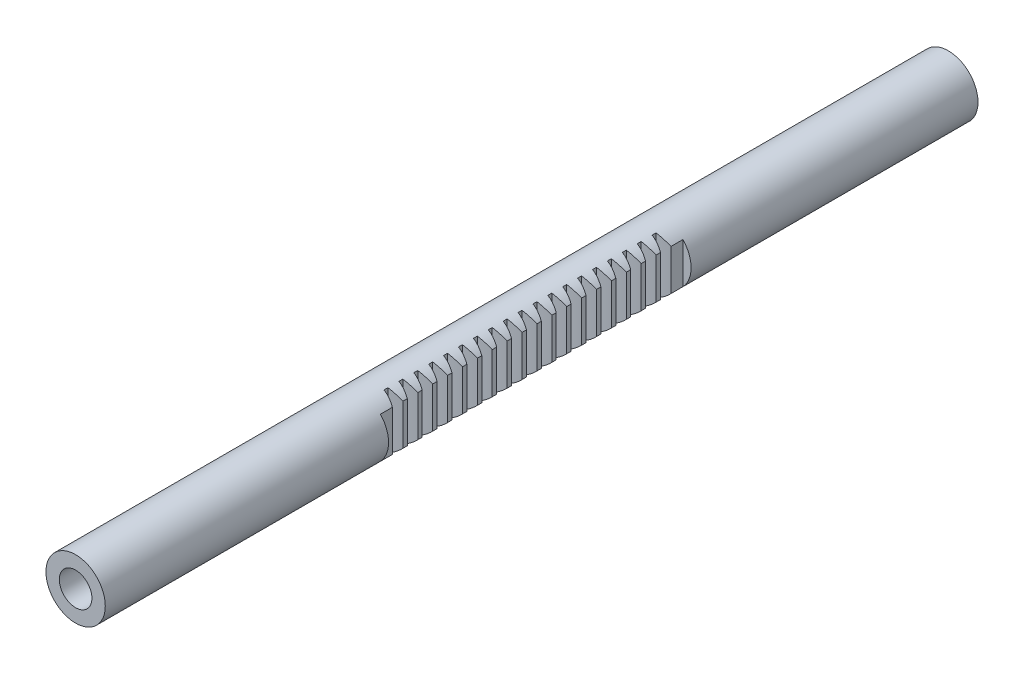
SolidWorks part; units mm, degrees
material "7050-T73510"
ref_plane "Front Plane" through (0, 0, 0) normal (0, 0, 1) x (1, 0, 0)
ref_plane "Top Plane" through (0, 0, 0) normal (0, 1, 0) x (1, 0, 0)
ref_plane "Right Plane" through (0, 0, 0) normal (1, 0, 0) x (0, 0, -1)
sketch "Sketch1" plane through (0, 0, 0) normal (0, 0, 1) x (1, 0, 0)
  circle A0 centre (0, 0) radius 12.75
extrude "Boss-Extrude1" add sketch "Sketch1" along normal blind 375
sketch "Sketch2" plane through (0, 0, 0) normal (0, 1, 0) x (1, 0, 0)
  line L0 (12.75, -123.2827) -> (12.75, -253.2827)
  line L1 (12.75, -375) -> (12.75, 0) construction
  line L2 (12.75, -123.2827) -> (9.25, -123.2827)
  line L3 (9.25, -123.2827) -> (9.25, -253.2827)
  line L4 (9.25, -253.2827) -> (12.75, -253.2827)
  point P5 (12.75, -188.2827)
  dimension "D1" = 130
  dimension "D2" = 3.5
extrude "Cut-Extrude1" cut sketch "Sketch2" against normal blind 45 and the other way blind 40
sketch "Sketch3" plane through (0, 0, 0) normal (0, 1, 0) x (1, 0, 0)
  line L0 (9.25, -190.5254) -> (9.25, -186.0254)
  line L1 (9.25, -253.2827) -> (9.25, -123.2827) construction
  line L2 (9.25, -188.2754) -> (4.25, -188.2754) construction
  line L3 (4.25, -189.1254) -> (4.25, -187.4254)
  arc A0 (4.25, -187.4254) -> (9.25, -186.0254) centre (1.5941, -168.3114) ccw
  arc A1 (4.25, -189.1254) -> (9.25, -190.5254) centre (1.5941, -208.2394) cw
  point P5 (9.25, -188.2754)
  point P10 (4.25, -188.2754)
extrude "Cut-Extrude2" cut sketch "Sketch3" against normal blind 45 and the other way blind 45
pattern_linear "LPattern1" count 10 spacing 6.4 along (0, 0, 1) count 10 spacing 6.4 along (0, 0, -1) of "Cut-Extrude2"
sketch "Sketch4" plane through (0, 0, 0) normal (0, 0, -1) x (-1, 0, 0)
  circle A0 centre (0, 0) radius 7
extrude "Cut-Extrude3" cut sketch "Sketch4" against normal blind 117.5
sketch "Sketch5" plane through (0, 0, 375) normal (0, 0, 1) x (1, 0, 0)
  circle A0 centre (0, 0) radius 7
extrude "Cut-Extrude4" cut sketch "Sketch5" against normal blind 117.5
